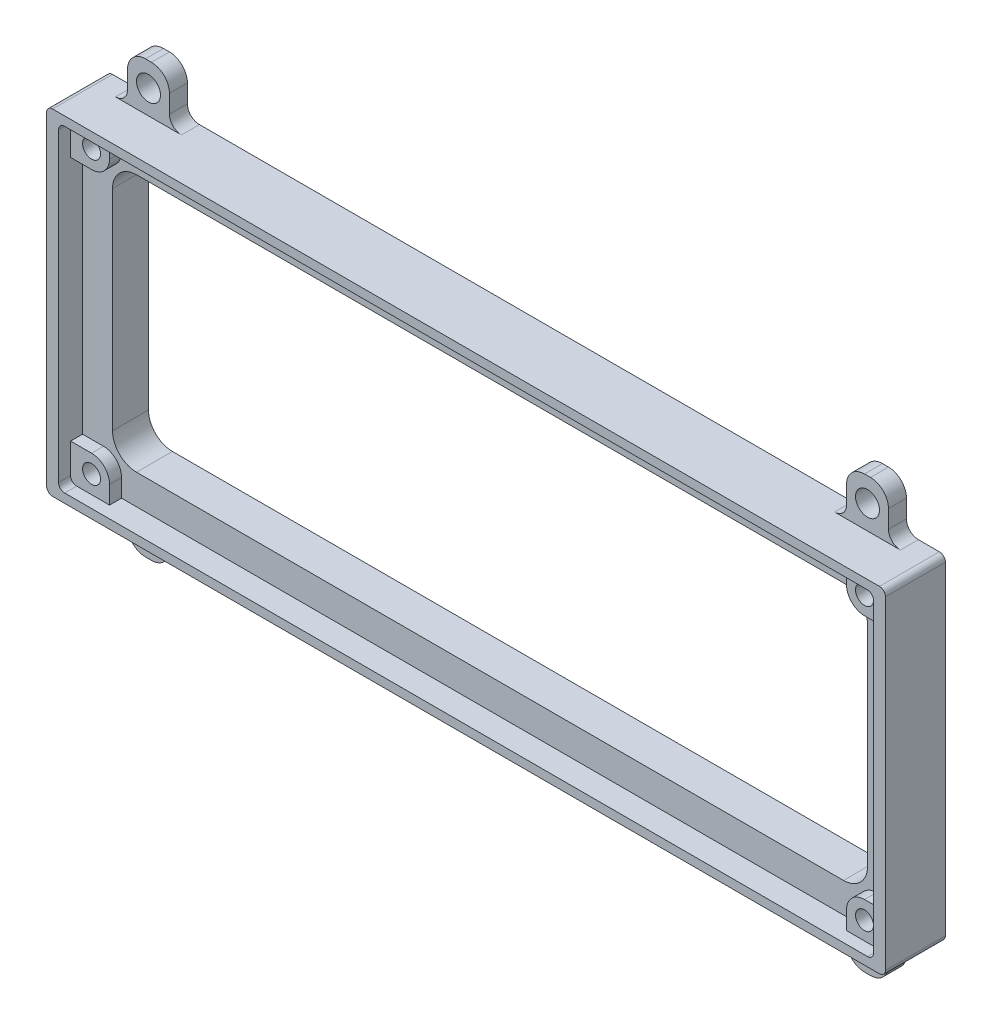
SolidWorks part; units mm, degrees
ref_plane "Front Plane" through (0, 0, 0) normal (0, 0, 1) x (1, 0, 0)
ref_plane "Top Plane" through (0, 0, 0) normal (0, 1, 0) x (1, 0, 0)
ref_plane "Right Plane" through (0, 0, 0) normal (1, 0, 0) x (0, 0, -1)
sketch "Sketch1" plane through (0, 0, 0) normal (0, 0, 1) x (1, 0, 0)
  line L0 (5.5, 51.5) -> (134.5, 51.5) construction
  line L1 (1, 0) -> (139, 0)
  line L2 (0, 1) -> (0, 55)
  line L3 (1, 56) -> (139, 56)
  line L4 (140, 1) -> (140, 55)
  line L5 (5.5, 51.5) -> (5.5, 4.5) construction
  line L7 (3, 54.5) -> (137, 54.5)
  line L8 (2, 53.5) -> (2, 2.5)
  line L9 (3, 1.5) -> (137, 1.5)
  line L10 (138, 53.5) -> (138, 2.5)
  circle A0 centre (5.5, 51.5) radius 1.5
  circle A1 centre (5.5, 4.5) radius 1.5
  circle A2 centre (134.5, 4.5) radius 1.5
  circle A3 centre (134.5, 51.5) radius 1.5
  arc A4 (139, 56) -> (140, 55) centre (139, 55) cw
  arc A5 (137, 54.5) -> (138, 53.5) centre (137, 53.5) cw
  arc A6 (137, 1.5) -> (138, 2.5) centre (137, 2.5) ccw
  arc A7 (139, 0) -> (140, 1) centre (139, 1) ccw
  arc A8 (2, 2.5) -> (3, 1.5) centre (3, 2.5) ccw
  arc A9 (1, 0) -> (0, 1) centre (1, 1) cw
  arc A10 (0, 55) -> (1, 56) centre (1, 55) cw
  arc A11 (3, 54.5) -> (2, 53.5) centre (3, 53.5) ccw
  point P13 (70, 51.5)
  point P14 (70, 56)
  point P15 (5.5, 28)
  point P16 (0, 28)
  point P21 (70, 54.5)
  point P22 (138, 28)
  point P27 (138, 54.5)
  point P30 (138, 1.5)
  point P33 (140, 0)
  point P38 (0, 0)
  point P41 (0, 56)
  point P44 (2, 54.5)
  dimension "D1" = 3
  dimension "D5" = 47
  dimension "D8" = 1
  dimension "D2" = 129
  dimension "D3" = 140
  dimension "D4" = 56
  dimension "D6" = 136
  dimension "D7" = 53
extrude "Boss-Extrude1" add sketch "Sketch1" against normal blind 6 contours L10 L7 L8 L9 A3 A2 A1 A0 | L1 L4 L3 L2 L7 L10 L9 L8 region at (1.3591, 1.3591, 0) region at (70, 28, 0)
extrude "Boss-Extrude2" add sketch "Sketch1<3>" along normal blind 4 contours L1 L4 L3 L2 L7 L10 L9 L8 region at (1.3591, 1.3591, 0)
sketch "Sketch1<3>" plane through (0, 0, 0) normal (0, 0, 1) x (1, 0, 0) same geometry as "Sketch1"
sketch "Sketch2" plane through (0, 0, 0) normal (0, 0, 1) x (1, 0, 0)
  line L0 (2, 53.5) -> (2, 2.5) construction
  line L1 (11, 49.5) -> (129, 49.5)
  line L2 (7, 45.5) -> (7, 10.5)
  line L3 (11, 6.5) -> (129, 6.5)
  line L4 (133, 45.5) -> (133, 10.5)
  line L5 (3, 54.5) -> (137, 54.5) construction
  line L6 (3, 54.5) -> (137, 54.5) construction
  line L7 (2, 53.5) -> (2, 2.5) construction
  arc A0 (129, 49.5) -> (133, 45.5) centre (129, 45.5) cw
  arc A1 (129, 6.5) -> (133, 10.5) centre (129, 10.5) ccw
  arc A2 (7, 10.5) -> (11, 6.5) centre (11, 10.5) ccw
  arc A3 (11, 49.5) -> (7, 45.5) centre (11, 45.5) ccw
  point P6 (2, 28)
  point P7 (7, 28)
  point P8 (70, 49.5)
  point P11 (70, 54.5)
  dimension "D3" = 4
  dimension "D1" = 5
  dimension "D2" = 5
extrude "Cut-Extrude1" cut sketch "Sketch2" against normal through all both and the other way through all
sketch "Sketch3" plane through (0, 0, -6) normal (0, 0, -1) x (-1, 0, 0)
  line L0 (-6.5, 0) -> (-6.5, -5)
  line L1 (-1, 0) -> (-139, 0) construction
  line L2 (-13.5, -5) -> (-13.5, 0)
  line L3 (-9.5, -8) -> (-10.5, -8)
  line L4 (-6.5, 0) -> (-13.5, 0)
  line L5 (-1, 56) -> (-139, 56) construction
  line L6 (-6.5, 56) -> (-13.5, 56)
  line L7 (-6.5, 56) -> (-6.5, 61)
  line L8 (-9.5, 64) -> (-10.5, 64)
  line L9 (-13.5, 56) -> (-13.5, 61)
  line L10 (-10, -4) -> (-10, 60) construction
  line L11 (-7, 45.5) -> (-7, 10.5) construction
  line L12 (-70, 6.5) -> (-70, 49.5) construction
  line L13 (-11, 6.5) -> (-129, 6.5) construction
  line L14 (-129, 49.5) -> (-11, 49.5) construction
  line L15 (-130, -4) -> (-130, 60) construction
  line L16 (-126.5, 56) -> (-126.5, 61)
  line L17 (-130.5, 64) -> (-129.5, 64)
  line L18 (-133.5, 56) -> (-133.5, 61)
  line L19 (-133.5, 56) -> (-126.5, 56)
  line L20 (-133.5, 0) -> (-133.5, -5)
  line L21 (-130.5, -8) -> (-129.5, -8)
  line L22 (-126.5, -5) -> (-126.5, 0)
  line L23 (-133.5, 0) -> (-126.5, 0)
  circle A0 centre (-10, -4) radius 2
  circle A1 centre (-10, 60) radius 2
  arc A2 (-10.5, 64) -> (-13.5, 61) centre (-10.5, 61) ccw
  arc A3 (-6.5, 61) -> (-9.5, 64) centre (-9.5, 61) ccw
  arc A4 (-6.5, -5) -> (-9.5, -8) centre (-9.5, -5) cw
  arc A5 (-13.5, -5) -> (-10.5, -8) centre (-10.5, -5) ccw
  arc A6 (-133.5, 61) -> (-130.5, 64) centre (-130.5, 61) cw
  arc A7 (-129.5, 64) -> (-126.5, 61) centre (-129.5, 61) cw
  circle A8 centre (-130, -4) radius 2
  circle A9 centre (-130, 60) radius 2
  arc A10 (-133.5, -5) -> (-130.5, -8) centre (-130.5, -5) ccw
  arc A11 (-126.5, -5) -> (-129.5, -8) centre (-129.5, -5) cw
  point P14 (-10, -8)
  point P17 (-10, 28)
  point P20 (-7, 28)
  point P27 (-6.5, -8)
  point P47 (-133.5, -8)
  dimension "D2" = 4
  dimension "D5" = 3
  dimension "D1" = 7
  dimension "D3" = 64
  dimension "D4" = 8
  dimension "D6" = 120
extrude "Boss-Extrude3" add sketch "Sketch3" against normal blind 3
fillet "Fillet1" radius 2 8 edges at (13.5, 56, -4.5) (6.5, 56, -4.5) (126.5, 56, -4.5) (133.5, 56, -4.5) (133.5, 0, -4.5) (126.5, 0, -4.5) (6.5, 0, -4.5) (13.5, 0, -4.5)
sketch "Sketch4" plane through (0, 0, 0) normal (0, 0, 1) x (1, 0, 0)
  line L0 (70, 49.5) -> (70, 6.5) construction
  line L1 (129, 49.5) -> (11, 49.5) construction
  line L2 (11, 6.5) -> (129, 6.5) construction
  line L3 (8.5, 51.5) -> (8.5, 54.8809)
  line L4 (6, 54.8809) -> (1.4615, 54.8809)
  line L5 (1.4615, 54.8809) -> (1.4615, 48.5)
  line L6 (1.4615, 48.5) -> (5.5, 48.5)
  line L7 (6, 54.8809) -> (8.5, 54.8809)
  line L8 (7, 28) -> (133, 28) construction
  line L9 (7, 45.5) -> (7, 10.5) construction
  line L10 (133, 10.5) -> (133, 45.5) construction
  line L11 (134, 54.8809) -> (131.5, 54.8809)
  line L12 (138.5385, 48.5) -> (134.5, 48.5)
  line L13 (138.5385, 54.8809) -> (138.5385, 48.5)
  line L14 (134, 54.8809) -> (138.5385, 54.8809)
  line L15 (131.5, 51.5) -> (131.5, 54.8809)
  line L16 (131.5, 4.5) -> (131.5, 1.1191)
  line L17 (134, 1.1191) -> (138.5385, 1.1191)
  line L18 (138.5385, 1.1191) -> (138.5385, 7.5)
  line L19 (138.5385, 7.5) -> (134.5, 7.5)
  line L20 (134, 1.1191) -> (131.5, 1.1191)
  line L21 (6, 1.1191) -> (8.5, 1.1191)
  line L22 (1.4615, 7.5) -> (5.5, 7.5)
  line L23 (1.4615, 1.1191) -> (1.4615, 7.5)
  line L24 (6, 1.1191) -> (1.4615, 1.1191)
  line L25 (8.5, 4.5) -> (8.5, 1.1191)
  circle A1 centre (5.5, 51.5) radius 1.5
  arc A8 (5.5, 48.5) -> (8.5, 51.5) centre (5.5, 51.5) ccw
  arc A9 (134.5, 48.5) -> (131.5, 51.5) centre (134.5, 51.5) cw
  circle A10 centre (134.5, 51.5) radius 1.5
  circle A11 centre (134.5, 4.5) radius 1.5
  arc A12 (134.5, 7.5) -> (131.5, 4.5) centre (134.5, 4.5) ccw
  arc A13 (5.5, 7.5) -> (8.5, 4.5) centre (5.5, 4.5) cw
  circle A14 centre (5.5, 4.5) radius 1.5
extrude "Boss-Extrude4" add sketch "Sketch4" along normal blind 2
